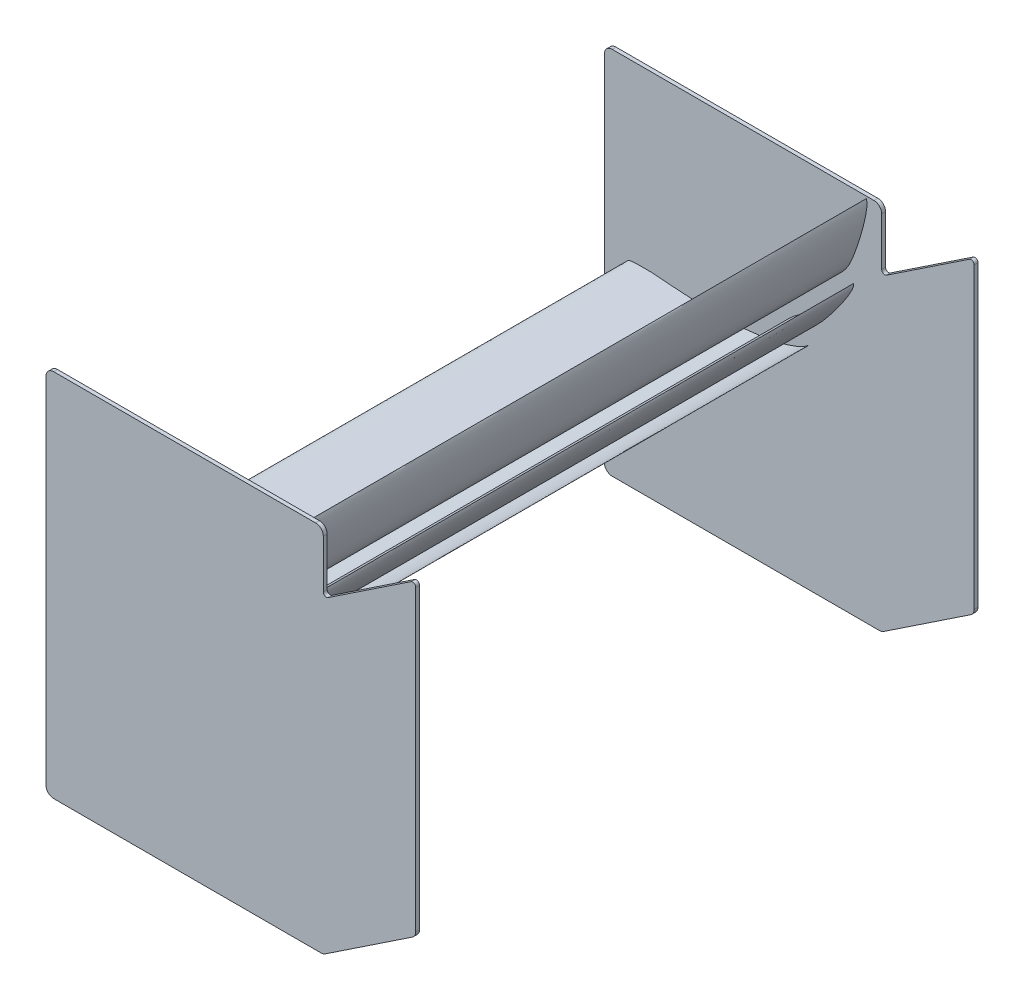
SolidWorks part; units mm, degrees
material "Pine"
ref_plane "Front Plane" through (0, 0, 0) normal (0, 0, 1) x (1, 0, 0)
ref_plane "Top Plane" through (0, 0, 0) normal (0, 1, 0) x (1, 0, 0)
ref_plane "Right Plane" through (0, 0, 0) normal (1, 0, 0) x (0, 0, -1)
sketch "Sketch1" plane through (0, 0, 0) normal (0, 0, 1) x (1, 0, 0)
  line L0 (298.3566, 31.3585) -> (0, 0) construction
  line L1 (-69.2385, 658.7606) -> (-5126.2087, 48772.6178) construction
  line L2 (-1246.1883, 0) -> (48753.8117, 0) construction
  line L3 (372.766, 156.866) -> (266.7, 50.8) construction
  line L4 (149.6578, 167.8422) -> (-28542.5976, 28860.0976) construction
  line L5 (-1272.5489, 50.8) -> (48727.4511, 50.8) construction
  line L6 (393.5927, 288.3462) -> (330.2, 152.4) construction
  line L7 (319.7693, 157.2639) -> (-36455.4607, 17305.8353) construction
  line L8 (-1068.692, 152.4) -> (48931.308, 152.4) construction
  spline S0 degree 3 poles (393.7214, 287.7433) (393.5624, 288.5103) (393.7007, 287.6555) (393.7816, 286.9087) (393.9854, 284.9679) (394.0117, 282.4521) (393.7445, 279.0677) (393.1113, 275.075) (392.1333, 270.5147) (390.7992, 265.4846) (389.1065, 260.052) (387.0662, 254.2928) (384.6886, 248.282) (382.002, 242.0922) (379.0353, 235.795) (375.823, 229.46) (372.4095, 223.1516) (368.8417, 216.9304) (365.1642, 210.8546) (361.4365, 204.9703) (357.7083, 199.3227) (354.0371, 193.9487) (350.4761, 188.8786) (347.0809, 184.1356) (343.9074, 179.7337) (340.9898, 175.6856) (338.4146, 171.924) (336.1932, 168.4193) (334.2406, 165.2135) (332.5565, 162.3267) (331.1614, 159.7869) (330.0437, 157.6351) (329.2915, 155.8603) (328.7602, 154.5543) (328.7696, 153.3945) (329.5605, 152.7152) (330.5323, 152.2097) (331.8099, 151.8878) (333.3002, 151.767) (334.9812, 151.8787) (336.8207, 152.2331) (338.7951, 152.8904) (340.8897, 153.85) (343.1084, 155.0818) (345.4223, 156.5984) (347.8072, 158.3949) (350.2426, 160.465) (352.7001, 162.8116) (355.1653, 165.4198) (357.6081, 168.2875) (360.006, 171.4084) (362.3141, 174.799) (364.5347, 178.4592) (366.6357, 182.4232) (368.6348, 186.6847) (370.6085, 191.1982) (372.524, 195.9513) (374.3974, 200.9051) (376.2349, 206.0233) (378.0459, 211.2596) (379.8209, 216.5688) (381.5551, 221.9024) (383.2253, 227.2222) (384.8167, 232.4908) (386.3202, 237.674) (387.7197, 242.7412) (389.0128, 247.6605) (390.1874, 252.403) (391.2421, 256.9381) (392.1695, 261.2388) (392.9646, 265.2792) (393.6239, 269.0355) (394.1472, 272.4855) (394.5308, 275.6102) (394.7756, 278.392) (394.8827, 280.8169) (394.8623, 282.8764) (394.6626, 284.618) (394.2998, 285.9922) (393.9161, 287.1924) (393.7214, 287.7433) (393.5624, 288.5103) (393.7007, 287.6555) knots -0.007483 -0.003649 -0.00098 0 0.001 0.004147 0.009748 0.018044 0.028864 0.041831 0.056714 0.073341 0.091508 0.111022 0.131662 0.153208 0.175433 0.19811 0.221011 0.243906 0.266573 0.28881 0.310405 0.331178 0.350944 0.369556 0.386865 0.402753 0.417196 0.43038 0.442363 0.453032 0.462284 0.470026 0.476177 0.48065 0.483553 0.486421 0.489953 0.494097 0.498851 0.504197 0.510125 0.516691 0.524012 0.532092 0.540898 0.550403 0.560581 0.571396 0.582828 0.59483 0.607347 0.620384 0.633969 0.6482 0.663194 0.678899 0.695227 0.712113 0.729459 0.747143 0.76501 0.782905 0.800688 0.818242 0.835449 0.852212 0.86843 0.884009 0.898855 0.912882 0.926011 0.938167 0.94929 0.959322 0.968217 0.975948 0.982474 0.987905 0.992517 0.996351 0.99902 1 1.001 1.004147 1.009748 only from (393.5927, 288.3462) to (393.5927, 288.3462)
  spline S1 degree 3 poles (297.4555, 30.517) (298.6067, 31.5796) (297.2837, 30.462) (296.0869, 29.5541) (292.9697, 27.2055) (288.6838, 24.5689) (282.6064, 21.5409) (275.1094, 18.5136) (266.2842, 15.4927) (256.2867, 12.5984) (245.2297, 9.9043) (233.2548, 7.4696) (220.5013, 5.3541) (207.1224, 3.5838) (193.271, 2.1832) (179.1018, 1.1645) (164.7709, 0.5184) (150.4305, 0.2264) (136.2266, 0.2724) (122.299, 0.6016) (108.7768, 1.1755) (95.7824, 1.9335) (83.4223, 2.8157) (71.7941, 3.7506) (60.9788, 4.6568) (51.0337, 5.4887) (41.9323, 6.0286) (33.6359, 6.2268) (26.1287, 6.2719) (19.445, 6.1855) (13.6539, 5.9609) (8.8136, 5.6605) (4.9963, 5.1217) (2.2101, 4.6873) (0.2315, 3.4766) (-0.1184, 1.4211) (0.0161, -0.7657) (0.7802, -3.2874) (2.1082, -5.9668) (4.0313, -8.7336) (6.5338, -11.522) (9.6944, -14.2298) (13.4969, -16.8321) (17.8941, -19.3669) (22.8776, -21.7713) (28.4141, -24.0094) (34.4715, -26.0522) (41.0258, -27.8479) (48.0364, -29.3876) (55.469, -30.6214) (63.2892, -31.5173) (71.4793, -31.9817) (80.0416, -32.0181) (89.0014, -31.5367) (98.3662, -30.5742) (108.137, -29.3086) (118.2585, -27.6963) (128.6806, -25.8051) (139.3477, -23.6832) (150.1899, -21.394) (161.1201, -18.9681) (172.0501, -16.4471) (182.8904, -13.8305) (193.5618, -11.1316) (203.9962, -8.37) (214.1247, -5.5497) (223.8901, -2.6992) (233.2301, 0.1722) (242.0913, 3.0357) (250.4195, 5.8757) (258.165, 8.6747) (265.2838, 11.4137) (271.7373, 14.0703) (277.4892, 16.6315) (282.5103, 19.0771) (286.7777, 21.3914) (290.2874, 23.5478) (293.0673, 25.6842) (295.0494, 27.7216) (296.7118, 29.6157) (297.4555, 30.517) (298.6067, 31.5796) (297.2837, 30.462) knots -0.007483 -0.003649 -0.00098 0 0.001 0.004147 0.009748 0.018044 0.028864 0.041831 0.056714 0.073341 0.091508 0.111022 0.131662 0.153208 0.175433 0.19811 0.221011 0.243906 0.266573 0.28881 0.310405 0.331178 0.350944 0.369556 0.386865 0.402753 0.417196 0.43038 0.442363 0.453032 0.462284 0.470026 0.476177 0.48065 0.483553 0.486421 0.489953 0.494097 0.498851 0.504197 0.510125 0.516691 0.524012 0.532092 0.540898 0.550403 0.560581 0.571396 0.582828 0.59483 0.607347 0.620384 0.633969 0.6482 0.663194 0.678899 0.695227 0.712113 0.729459 0.747143 0.76501 0.782905 0.800688 0.818242 0.835449 0.852212 0.86843 0.884009 0.898855 0.912882 0.926011 0.938167 0.94929 0.959322 0.968217 0.975948 0.982474 0.987905 0.992517 0.996351 0.99902 1 1.001 1.004147 1.009748 only from (298.3566, 31.3585) to (298.3566, 31.3585)
  spline S2 degree 3 poles (372.6807, 156.2555) (372.7936, 157.0306) (372.6312, 156.1801) (372.4518, 155.4507) (371.9796, 153.5572) (371.1439, 151.1841) (369.7351, 148.0952) (367.7746, 144.5599) (365.2959, 140.6091) (362.3218, 136.3386) (358.8731, 131.8126) (354.9861, 127.0985) (350.6961, 122.2634) (346.0545, 117.3657) (341.1129, 112.463) (335.9277, 107.6087) (330.5624, 102.8483) (325.082, 98.2225) (319.5483, 93.7709) (314.0328, 89.5164) (308.5979, 85.4845) (303.3101, 81.6902) (298.2297, 78.1438) (293.4171, 74.8481) (288.9294, 71.7971) (284.8032, 68.991) (281.0968, 66.337) (277.8107, 63.8034) (274.8794, 61.4588) (272.3095, 59.3221) (270.1299, 57.4126) (268.3436, 55.7728) (267.0298, 54.3623) (266.0839, 53.3168) (265.696, 52.2238) (266.2068, 51.3149) (266.9472, 50.5075) (268.0376, 49.7681) (269.3967, 49.1448) (271.0146, 48.6749) (272.8644, 48.3788) (274.9445, 48.3211) (277.2409, 48.5064) (279.7471, 48.9051) (282.4402, 49.5389) (285.2957, 50.4114) (288.2923, 51.5237) (291.4042, 52.8882) (294.6128, 54.4959) (297.8891, 56.3552) (301.2097, 58.4678) (304.5383, 60.8645) (307.8768, 63.5445) (311.2069, 66.5509) (314.5429, 69.8716) (317.9414, 73.4379) (321.367, 77.2492) (324.8216, 81.2635) (328.2989, 85.4445) (331.7916, 89.7457) (335.2754, 94.1276) (338.7293, 98.5464) (342.1182, 102.9742) (345.4156, 107.3807) (348.6011, 111.7371) (351.6493, 116.0201) (354.547, 120.2005) (357.2727, 124.2551) (359.8149, 128.1561) (362.1574, 131.8802) (364.2864, 135.405) (366.1907, 138.7093) (367.8624, 141.7722) (369.2915, 144.5773) (370.4731, 147.1076) (371.4031, 149.3497) (372.0883, 151.2919) (372.4962, 152.9968) (372.6253, 154.4122) (372.6753, 155.6713) (372.6807, 156.2555) (372.7936, 157.0306) (372.6312, 156.1801) knots -0.007483 -0.003649 -0.00098 0 0.001 0.004147 0.009748 0.018044 0.028864 0.041831 0.056714 0.073341 0.091508 0.111022 0.131662 0.153208 0.175433 0.19811 0.221011 0.243906 0.266573 0.28881 0.310405 0.331178 0.350944 0.369556 0.386865 0.402753 0.417196 0.43038 0.442363 0.453032 0.462284 0.470026 0.476177 0.48065 0.483553 0.486421 0.489953 0.494097 0.498851 0.504197 0.510125 0.516691 0.524012 0.532092 0.540898 0.550403 0.560581 0.571396 0.582828 0.59483 0.607347 0.620384 0.633969 0.6482 0.663194 0.678899 0.695227 0.712113 0.729459 0.747143 0.76501 0.782905 0.800688 0.818242 0.835449 0.852212 0.86843 0.884009 0.898855 0.912882 0.926011 0.938167 0.94929 0.959322 0.968217 0.975948 0.982474 0.987905 0.992517 0.996351 0.99902 1 1.001 1.004147 1.009748 only from (372.766, 156.866) to (372.766, 156.866)
  dimension "D1" = 300
  dimension "D2" = 6
  dimension "D3" = 330.2
  dimension "D4" = 152.4
  dimension "D5" = 150
  dimension "D6" = 45
  dimension "D7" = 150
  dimension "D8" = 65
  dimension "D9" = 266.7
  dimension "D10" = 50.8
extrude "Boss-Extrude1" add sketch "Sketch1" along normal blind 457.2
sketch "Sketch2" plane through (0, 0, 457.2) normal (0, 0, 1) x (1, 0, 0)
  line L1 (-38.1, 292.1) -> (571.5, 292.1)
  line L2 (-38.1, 292.1) -> (-38.1, -317.5)
  line L3 (-38.1, -317.5) -> (571.5, -317.5)
  line L4 (571.5, 292.1) -> (571.5, -317.5)
  line L5 (-38.1, 292.1) -> (571.5, -317.5) construction
  line L6 (-38.1, -317.5) -> (571.5, 292.1) construction
  point P4 (266.7, -12.7)
  dimension "D1" = 609.6
  dimension "D2" = 609.6
  dimension "D3" = 38.1
  dimension "D4" = 317.5
extrude "Boss-Extrude2" add sketch "Sketch2" along normal blind 6.35 contours L2 L3 L4 L1
sketch "Sketch3" plane through (0, 0, 463.55) normal (0, 0, 1) x (1, 0, 0)
  line L4 (419.1, 292.1) -> (419.1, 190.5)
  line L5 (-38.1, 292.1) -> (571.5, 292.1) construction
  line L6 (571.5, -215.9) -> (419.1, -317.5)
  line L7 (571.5, 292.1) -> (571.5, -317.5) construction
  line L8 (-38.1, -317.5) -> (571.5, -317.5) construction
  line L13 (419.1, 190.5) -> (571.5, 292.1)
  line L14 (571.5, 292.1) -> (419.1, 292.1)
  line L15 (419.1, -317.5) -> (571.5, -317.5)
  line L16 (571.5, -317.5) -> (571.5, -215.9)
  dimension "D1" = 152.4
  dimension "D2" = 101.6
  dimension "D3" = 152.4
  dimension "D4" = 101.6
extrude "Cut-Extrude1" cut sketch "Sketch3" against normal through all
fillet "Fillet1" radius 12.7 5 edges at (-38.1, -317.5, 460.375) (-38.1, 292.1, 460.375) (419.1, 292.1, 460.375) (419.1, -317.5, 460.375) (571.5, -215.9, 460.375)
fillet "Fillet2" radius 5.08 2 edges at (571.5, 292.1, 460.375) (419.1, 190.5, 460.375)
mirror "Mirror1" about plane through (2.488, -6.4381, 0) normal (0, 0, -1) of bodies 105
ref_axis "Axis1" through (0, 0, 0) along (0, 0, 1)
ref_axis "Axis2" through (298.3566, 31.3585, 0) along (0, 0, 1)
